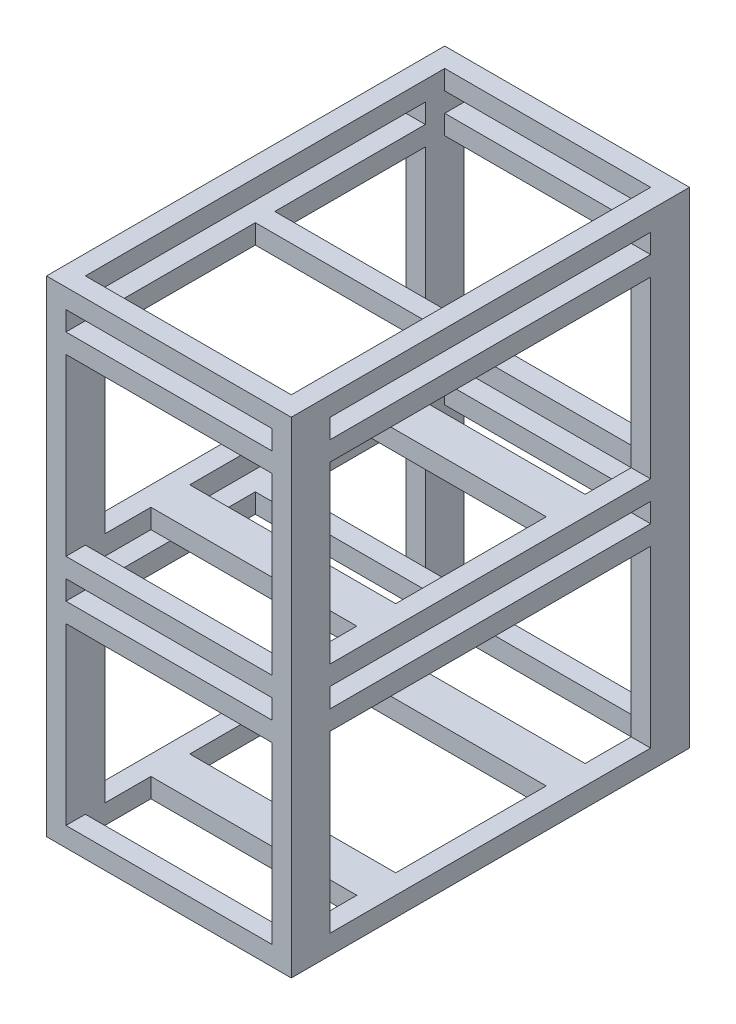
SolidWorks part; units mm, degrees
ref_plane "Front Plane" through (0, 0, 0) normal (0, 0, 1) x (1, 0, 0)
ref_plane "Top Plane" through (0, 0, 0) normal (0, 1, 0) x (1, 0, 0)
ref_plane "Right Plane" through (0, 0, 0) normal (1, 0, 0) x (0, 0, -1)
sketch "Sketch1" plane through (0, 0, 0) normal (0, 1, 0) x (1, 0, 0)
  line L7 (-126, -205) -> (126, -205)
  line L8 (-126, -205) -> (-126, 205)
  line L9 (-126, 205) -> (126, 205)
  line L10 (126, -205) -> (126, 205)
  line L11 (-126, -205) -> (126, 205) construction
  line L12 (-126, 205) -> (126, -205) construction
  line L13 (-106, -185) -> (106, -185)
  line L14 (-106, -185) -> (-106, 185)
  line L15 (-106, 185) -> (106, 185)
  line L16 (106, -185) -> (106, 185)
  line L17 (-106, -185) -> (106, 185) construction
  line L18 (-106, 185) -> (106, -185) construction
  point P0 (0, 0)
  point P6 (0, 0)
  point P11 (0, 0)
  dimension "D1" = 370
  dimension "D2" = 212
  dimension "D3" = 20
  dimension "D4" = 20
extrude "Boss-Extrude1" add sketch "Sketch1" against normal blind 20 contours L16 L13 L14 L15 | L7 L10 L9 L8 region at (-121.1875, 0, 0)
sketch "Sketch2" plane through (0, 0, 0) normal (0, 1, 0) x (1, 0, 0)
  line L0 (-126, -205) -> (126, -205) construction
  line L1 (126, -205) -> (126, 205) construction
  line L2 (-126, 205) -> (126, 205) construction
  line L3 (-126, -205) -> (-126, 205) construction
  line L4 (-126, -205) -> (126, -205)
  line L5 (126, -205) -> (126, 205)
  line L6 (-126, 205) -> (126, 205)
  line L7 (-126, -205) -> (-126, 205)
  line L9 (-126, -205) -> (-106, -205)
  line L10 (-126, -205) -> (-126, -165)
  line L11 (-126, -165) -> (-106, -165)
  line L12 (-106, -205) -> (-106, -165)
  line L13 (126, -205) -> (106, -205)
  line L14 (126, -205) -> (126, -165)
  line L15 (126, -165) -> (106, -165)
  line L16 (106, -205) -> (106, -165)
  line L17 (126, 205) -> (106, 205)
  line L18 (126, 205) -> (126, 165)
  line L19 (126, 165) -> (106, 165)
  line L20 (106, 205) -> (106, 165)
  line L21 (-126, 205) -> (-106, 205)
  line L22 (-126, 205) -> (-126, 165)
  line L23 (-126, 165) -> (-106, 165)
  line L24 (-106, 205) -> (-106, 165)
  line M23 (-126, -205) -> (126, -205)
  line M24 (126, -205) -> (126, 205)
  line M25 (126, 205) -> (-126, 205)
  line M26 (-126, 205) -> (-126, -205)
  dimension "D1" = 40
  dimension "D2" = 20
extrude "Boss-Extrude2" add sketch "Sketch2" along normal blind 460 contours L24 L23 M25 M26 | L12 L11 L7 M23 | L16 L15 M23 M24 | L20 L19 M25 M24 region at (-116, 0, 185) region at (116, 0, 185) region at (-116, 0, -185) region at (116, 0, -185)
extrude "Boss-Extrude3" add sketch "Sketch1<3>" along normal blind 20 from surface contours L7 L10 L9 L8 | L16 L13 L14 L15 region at (-121.1875, 0, 0) starting at face at (-116, 460, 185)
sketch "Sketch1<3>" plane through (0, 0, 0) normal (0, 1, 0) x (1, 0, 0) same geometry as "Sketch1"
sketch "Sketch3" plane through (0, 0, 0) normal (0, 1, 0) x (1, 0, 0)
  line L0 (-106, -185) -> (-106, -205) construction
  line L1 (-106, -117.5) -> (106, -117.5)
  line L2 (-106, -117.5) -> (-106, -77.5)
  line L3 (-106, -77.5) -> (106, -77.5)
  line L4 (106, -117.5) -> (106, -77.5)
  line L5 (106, -185) -> (106, -205) construction
  line L6 (-106, -205) -> (106, -205) construction
  line L7 (-106, 77.5) -> (106, 77.5)
  line L8 (-106, 77.5) -> (-106, 117.5)
  line L9 (-106, 117.5) -> (106, 117.5)
  line L10 (106, 77.5) -> (106, 117.5)
  line L11 (-106, 205) -> (106, 205) construction
  point P14 (106, -97.5)
  point P15 (106, 97.5)
  dimension "D1" = 107.5
  dimension "D2" = 40
  dimension "D3" = 107.5
extrude "Boss-Extrude4" add sketch "Sketch3" against normal blind 20
sketch "Sketch4" plane through (0, 0, 165) normal (0, 0, -1) x (-1, 0, 0)
  line L0 (-106, 460) -> (-106, 0) construction
  line L1 (-106, 200) -> (-126, 200)
  line L2 (-106, 200) -> (-106, 180)
  line L3 (-106, 180) -> (-126, 180)
  line L4 (-126, 200) -> (-126, 180)
  line L5 (-126, 460) -> (-126, 0) construction
  line L6 (126, 460) -> (126, 0) construction
  line L7 (126, 200) -> (106, 200)
  line L8 (126, 200) -> (126, 180)
  line L9 (126, 180) -> (106, 180)
  line L10 (106, 200) -> (106, 180)
  line L11 (106, 460) -> (106, 0) construction
  line L12 (-126, 0) -> (-106, 0) construction
  dimension "D1" = 200
  dimension "D2" = 20
extrude "Boss-Extrude5" add sketch "Sketch4" along normal up to surface (330 mm away) up to face at (116, 230, -165)
sketch "Sketch5" plane through (0, 200, 0) normal (0, 1, 0) x (1, 0, 0)
  line L0 (116, -165) -> (116, -97.5) construction
  line L1 (106, -165) -> (126, -165) construction
  line L3 (-106, -185) -> (106, -185) construction
  line L4 (-106, -185) -> (106, -185) construction
  circle A0 centre (116, -97.5) radius 2.75
  dimension "D2" = 5.5
  dimension "D1" = 87.5
sketch "Sketch6" plane through (106, 0, 0) normal (-1, 0, 0) x (0, 0, 1)
  line L0 (-165, 200) -> (165, 200) construction
  line L1 (-165, 200) -> (165, 200)
  line L2 (205, 460) -> (205, 0) construction
  line L3 (205, 200) -> (185, 200)
  line L4 (205, 200) -> (205, 180)
  line L5 (205, 180) -> (185, 180)
  line L6 (185, 200) -> (185, 180)
  line L7 (-205, 460) -> (-205, 0) construction
  line L8 (-205, 200) -> (-185, 200)
  line L9 (-205, 200) -> (-205, 180)
  line L10 (-205, 180) -> (-185, 180)
  line L11 (-185, 200) -> (-185, 180)
  line L12 (-165, 180) -> (165, 180) construction
  line L13 (-10, 200) -> (10, 200)
  line L14 (-10, 200) -> (-10, 180)
  line L15 (-10, 180) -> (10, 180)
  line L16 (10, 200) -> (10, 180)
  line L17 (-10, 190) -> (10, 190) construction
  line L18 (0, 190) -> (0, 200) construction
  line M7 (205, 0) -> (205, 460)
  line M13 (-205, 460) -> (-205, 0)
  line M16 (-165, 180) -> (165, 180)
  dimension "D1" = 20
extrude "Boss-Extrude6" add sketch "Sketch6" along normal up to surface (212 mm away) contours L11 L8 L10 M13 | L16 L1 L14 M16 | L3 L6 L5 M7 region at (106, 190, 0) region at (106, 190, 195) region at (106, 190, -195) up to face at (-106, 330, 0)
pattern_linear "LPattern2" count 2 spacing 240 along (0, 1, 0) of "Boss-Extrude5"
pattern_linear "LPattern1" count 2 spacing 240 along (0, 1, 0) of "Boss-Extrude6"
pattern_linear "LPattern3" count 2 spacing 240 along (0, 1, 0) of "Boss-Extrude1", "Boss-Extrude4"
